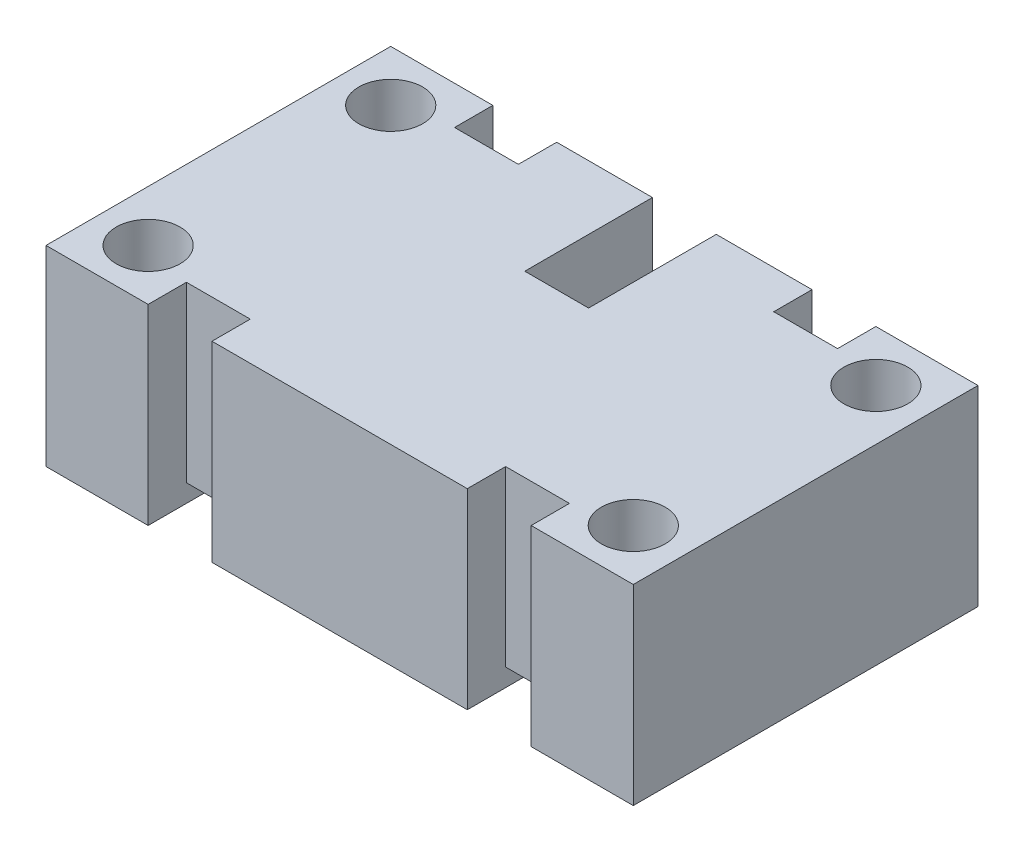
SolidWorks part; units mm, degrees
ref_plane "Front Plane" through (0, 0, 0) normal (0, 0, 1) x (1, 0, 0)
ref_plane "Top Plane" through (0, 0, 0) normal (0, 1, 0) x (1, 0, 0)
ref_plane "Right Plane" through (0, 0, 0) normal (1, 0, 0) x (0, 0, -1)
sketch "Sketch1" plane through (0, 0, 0) normal (0, 1, 0) x (1, 0, 0)
  line L0 (13.1053, 16.2424) -> (13.1053, -7.99) construction
  line L1 (-16.1047, 17.5818) -> (9.9303, 17.5818)
  line L2 (-16.1047, 17.5818) -> (-16.1047, -16.7082)
  line L3 (-16.1047, -16.7082) -> (-5.9447, -16.7082)
  line L4 (42.3153, 17.5818) -> (42.3153, -16.7082)
  line L5 (0.4053, -16.7082) -> (42.3153, -16.7082)
  line L6 (9.9303, 17.5818) -> (9.9303, 4.8818)
  line L7 (9.9303, 4.8818) -> (16.2803, 4.8818)
  line L8 (16.2803, 17.5818) -> (16.2803, 4.8818)
  line L9 (-5.9447, 17.5818) -> (0.4053, 17.5818)
  line L10 (-5.9447, 17.5818) -> (-5.9447, 13.7718)
  line L11 (-5.9447, 13.7718) -> (0.4053, 13.7718)
  line L12 (0.4053, 17.5818) -> (0.4053, 13.7718)
  line L13 (-16.1047, 0.4368) -> (42.3153, 0.4368) construction
  line L14 (25.8053, 13.7718) -> (32.1553, 13.7718)
  line L15 (32.1553, 13.7718) -> (32.1553, 17.5818)
  line L16 (32.1553, 17.5818) -> (25.8053, 17.5818)
  line L17 (25.8053, 17.5818) -> (25.8053, 13.7718)
  line L18 (-5.9447, -16.7082) -> (-5.9447, -12.8982)
  line L19 (-5.9447, -12.8982) -> (0.4053, -12.8982)
  line L20 (0.4053, -16.7082) -> (0.4053, -12.8982)
  line L21 (25.8053, -16.7082) -> (25.8053, -12.8982)
  line L22 (32.1553, -12.8982) -> (25.8053, -12.8982)
  line L23 (32.1553, -12.8982) -> (32.1553, -16.7082)
  line L24 (32.1553, -16.7082) -> (25.8053, -16.7082)
  line L25 (16.2803, 17.5818) -> (42.3153, 17.5818)
  circle A0 centre (-11.0247, 12.5018) radius 3.175
  circle A1 centre (37.2353, 12.5018) radius 3.175
  circle A2 centre (-11.0247, -11.6282) radius 3.175
  circle A3 centre (37.2353, -11.6282) radius 3.175
  circle A4 centre (-11.0247, 12.5018) radius 2.159
  circle A5 centre (-11.0247, -11.6282) radius 2.159
  circle A6 centre (37.2353, -11.6282) radius 2.159
  circle A7 centre (37.2353, 12.5018) radius 2.159
  point P25 (25.8053, 15.6768)
  point P26 (0.4053, 15.6768)
  point P27 (25.8053, 13.7718)
  point P28 (25.8053, 17.5818)
  point P29 (32.1553, 17.5818)
  point P30 (32.1553, 13.7718)
  point P44 (32.1553, -16.7082)
  point P45 (24.8596, -16.7082)
  dimension "D5" = 6.35
  dimension "D6" = 6.35
  dimension "D7" = 6.35
  dimension "D8" = 6.35
  dimension "D9" = 4.318
  dimension "D10" = 4.318
  dimension "D11" = 4.318
  dimension "D12" = 4.318
  dimension "D2" = 34.29
  dimension "D3" = 6.35
  dimension "D4" = 3.175
  dimension "D13" = 5.08
  dimension "D14" = 5.08
  dimension "D15" = 5.08
  dimension "D16" = 5.08
  dimension "D17" = 5.08
  dimension "D18" = 5.08
  dimension "D19" = 5.08
  dimension "D20" = 5.08
  dimension "D21" = 3.81
  dimension "D22" = 6.35
  dimension "D23" = 12.7
  dimension "D24" = 16.51
  dimension "D25" = 16.51
  dimension "D26" = 16.51
  dimension "D27" = 3.81
  dimension "D28" = 6.35
  dimension "D29" = 6.35
  dimension "D30" = 25.4
  dimension "D31" = 29.21
extrude "Boss-Extrude1" add sketch "Sketch1" along normal blind 19.05 contours L22 L23 L3 L4 L1 L15 L14 L17 L12 L11 L10 L2 L18 L19 L20 L21 A3 A2 A1 A0 L8 L7 L6 | L13 L2 L3 L18 L19 L20 L21 L22 L23 L4 A3 A2 region at (13.1053, 0, 0.0755)
extrude "Boss-Extrude2" add sketch "Sketch1<3>" along normal blind 2.54 contours A0 A4 | A2 A5 | A1 A7 | A3 A6 region at (-14.1099, 0, -12.5018) region at (34.1501, 0, -12.5018) region at (-14.1099, 0, 11.6282) region at (34.1501, 0, 11.6282)
sketch "Sketch1<3>" plane through (0, 0, 0) normal (0, 1, 0) x (1, 0, 0) same geometry as "Sketch1"
sketch "Sketch2" plane through (0, 0, 16.7082) normal (0, 0, 1) x (1, 0, 0)
  line L0 (0.4053, 19.05) -> (0.4053, 0) construction
  line L1 (-5.9447, 0) -> (0.4053, 0)
  line L2 (-5.9447, 0) -> (-5.9447, 1.778)
  line L3 (-5.9447, 1.778) -> (0.4053, 1.778)
  line L4 (0.4053, 0) -> (0.4053, 1.778)
  line L5 (32.1553, 19.05) -> (32.1553, 0) construction
  line L6 (25.8053, 0) -> (32.1553, 0)
  line L7 (25.8053, 0) -> (25.8053, 1.778)
  line L8 (25.8053, 1.778) -> (32.1553, 1.778)
  line L9 (32.1553, 0) -> (32.1553, 1.778)
  dimension "D1" = 1.778
  dimension "D2" = 1.778
extrude "Cut-Extrude2" cut sketch "Sketch2" against normal through all contours L3 L2 L1 | L6 L9 L8 region at (-2.7697, 0.889, 16.7082) region at (28.9803, 0.889, 16.7082)
